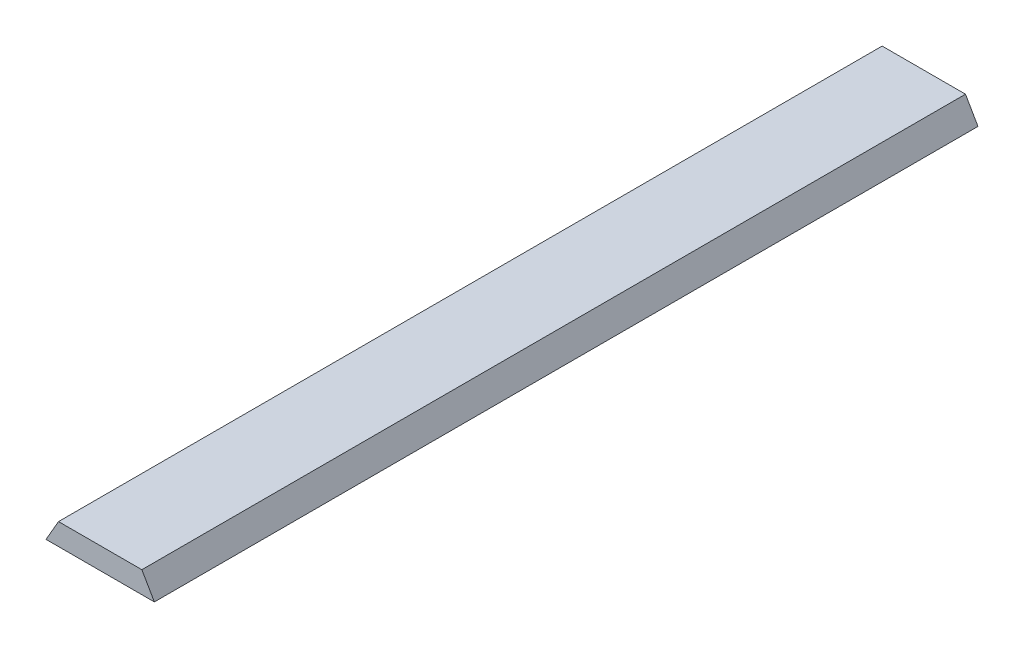
SolidWorks part; units mm, degrees
ref_plane "Front Plane" through (0, 0, 0) normal (0, 0, 1) x (1, 0, 0)
ref_plane "Top Plane" through (0, 0, 0) normal (0, 1, 0) x (1, 0, 0)
ref_plane "Right Plane" through (0, 0, 0) normal (1, 0, 0) x (0, 0, -1)
sketch "Sketch2" plane through (0, 0, 0) normal (0, 0, 1) x (1, 0, 0)
  line L1 (-5, -1) -> (5, -1)
  line L2 (-5, -1) -> (-5, 1)
  line L3 (-5, 1) -> (5, 1)
  line L4 (5, -1) -> (5, 1)
  line L5 (-5, -1) -> (5, 1) construction
  line L6 (-5, 1) -> (5, -1) construction
  point P0 (0, 0)
  dimension "D1" = 10
  dimension "D2" = 2
extrude "Boss-Extrude1" add sketch "Sketch2" along normal blind 76
chamfer "Chamfer1" distance 2 angle 30 2 edges at (5, 1, 38) (-5, 1, 38) first distance on face at (5, 0, 38) first distance on face at (-5, 0, 38)
